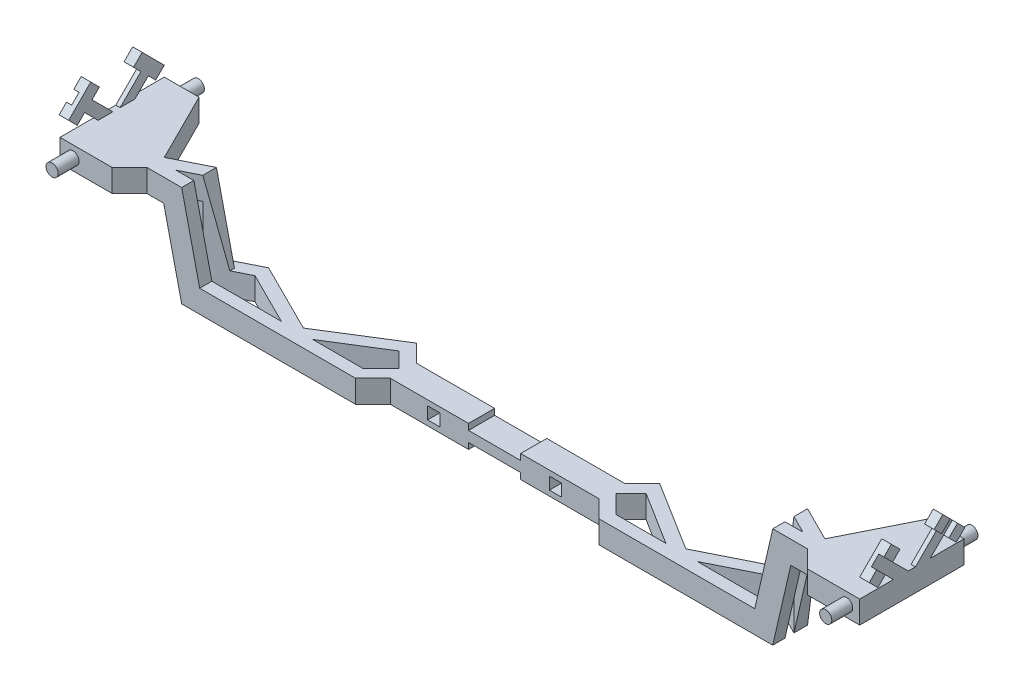
SolidWorks part; units mm, degrees
material "PBT General Purpose"
ref_plane "Front Plane" through (0, 0, 0) normal (0, 0, 1) x (1, 0, 0)
ref_plane "Top Plane" through (0, 0, 0) normal (0, 1, 0) x (1, 0, 0)
ref_plane "Right Plane" through (0, 0, 0) normal (1, 0, 0) x (0, 0, -1)
sketch "Sketch1" plane through (0, 0, 0) normal (0, -1, 0) x (0, 0, 1)
  line L1 (-15, -57.5) -> (15, -57.5)
  line L2 (-15, -57.5) -> (-15, 57.5)
  line L3 (-15, 57.5) -> (15, 57.5)
  line L4 (15, -57.5) -> (15, 57.5)
  line L5 (-15, -57.5) -> (15, 57.5) construction
  line L6 (-15, 57.5) -> (15, -57.5) construction
  point P0 (0, 0)
  dimension "D1" = 115
  dimension "D2" = 30
extrude "Boss-Extrude1" add sketch "Sketch1" against normal blind 6.5
sketch "Sketch2" plane through (0, 0, 0) normal (0, 0, 1) x (1, 0, 0)
  line L1 (-57.5, 3.25) -> (-53.75, 3.25) construction
  line L2 (-57.5, 6.5) -> (-57.5, 0) construction
  circle A0 centre (-53.75, 3.25) radius 1.75
  dimension "D1" = 3.5
  dimension "D2" = 3.75
extrude "Boss-Extrude2" add sketch "Sketch2" against normal blind 21.025 and the other way blind 21.025
sketch "Sketch3" [suppressed] plane through (-11.6078, -26.3195, 0) normal (0, 0, 1) x (-1, 0, 0)
  line L0 (38.3922, -32.8195) -> (38.3922, -26.3195) construction
  line L1 (38.1407, -29.5811) -> (31.4445, -29.9941) construction
  line L14 (37.9239, -29.0985) -> (34.3773, -25.5312)
  arc A1 (37.9753, -30.0988) -> (37.9239, -29.0985) centre (37.3921, -29.6273) ccw
  circle A2 centre (33.1422, -29.5695) radius 1.75 construction
  arc A5 (34.5556, -33.6079) -> (37.9753, -30.0988) centre (17.3684, -13.4374) ccw
  point P0 (38.3922, -29.5695)
  dimension "D1" = 1.5
sketch "Sketch4" plane through (-57.5, 0, 0) normal (-1, 0, 0) x (0, 0, 1)
  line L0 (0, -1000) -> (0, 49000) construction
  line L1 (15, 4.53) -> (15, 7.4362) construction
  line L2 (15, 7.4362) -> (17.009, 7.4362) construction
  line L3 (-9.1587, 10.3713) -> (-11.6392, 12.8374)
  line L4 (2.5, 22.03) -> (-2.5, 22.03) construction
  line L5 (-7.4017, 17.0996) -> (-13.7471, 10.7171)
  line L6 (-17.009, 7.4362) -> (-15, 7.4362) construction
  line L7 (-15, 7.4362) -> (-15, 4.53) construction
  line L8 (-11.28, 8.25) -> (-4.916, 14.614)
  line L9 (-2.5, 17.03) -> (2.5, 17.03) construction
  line L10 (-7.0374, 12.4926) -> (-9.5241, 14.9649)
  line L11 (0, 22.03) -> (0, 17.03) construction
  line L12 (15, 6.5) -> (-15, 6.5) construction
  line L13 (-7.4017, 17.0996) -> (-4.916, 14.614)
  line L14 (-13.7471, 10.7171) -> (-11.28, 8.25)
  line L15 (-9.1587, 10.3713) -> (0, 1.2126)
  line L16 (-7.0374, 12.4926) -> (0, 5.4553)
  line L17 (7.0374, 12.4926) -> (0, 5.4553)
  line L18 (9.1587, 10.3713) -> (0, 1.2126)
  line L19 (13.7471, 10.7171) -> (11.28, 8.25)
  line L20 (7.4017, 17.0996) -> (4.916, 14.614)
  line L21 (11.28, 8.25) -> (4.916, 14.614)
  line L22 (7.4017, 17.0996) -> (13.7471, 10.7171)
  line L23 (7.0374, 12.4926) -> (9.5241, 14.9649)
  line L24 (9.1587, 10.3713) -> (11.6392, 12.8374)
  line M3 (15, 6.5) -> (-15, 6.5)
  dimension "D1" = 10.53
  dimension "D2" = 3
  dimension "D3" = 9
  dimension "D4" = 3
  dimension "D5" = 1.75
extrude "Boss-Extrude3" add sketch "Sketch4" against normal blind 1.25 contours L18 L17 L16 L15 M3 | L18 L21 L17 M3 | L21 L24 L22 L23 | L21 L23 L22 L20 | L24 L21 L19 L22 | L16 L8 L15 M3 | L5 L14 L8 L3 | L8 L10 L5 L3 | L13 L5 L10 L8 region at (-57.5, 10.5437, -11.4551) region at (-57.5, 12.667, -9.3394) region at (-57.5, 9.004, -5.518) region at (-57.5, 14.7939, -7.2201) region at (-57.5, 4.6801, 0) region at (-57.5, 9.004, 5.518) region at (-57.5, 12.667, 9.3394) region at (-57.5, 14.7939, 7.2201) region at (-57.5, 10.5437, 11.4551)
extrude "Boss-Extrude4" add sketch "Sketch4<3>" along normal blind 1.5 contours L5 L14 L8 L3 | L13 L5 L10 L8 | L21 L23 L22 L20 | L24 L21 L19 L22 region at (-57.5, 10.5437, -11.4551) region at (-57.5, 14.7939, -7.2201) region at (-57.5, 10.5437, 11.4551) region at (-57.5, 14.7939, 7.2201)
sketch "Sketch4<3>" plane through (-57.5, 0, 0) normal (-1, 0, 0) x (0, 0, 1) same geometry as "Sketch4"
ref_plane "Plane1" through (57.5, 0, 0) normal (1, 0, 0) x (0, 0, -1)
mirror "Mirror1" about plane through (57.5, 0, 0) normal (1, 0, 0) of bodies 105
sketch "Sketch6" plane through (0, 6.5, 0) normal (0, 1, 0) x (1, 0, 0)
  line L0 (27.5, -5) -> (87.5, -5)
  line L1 (-57.5, 15) -> (172.5, 15) construction
  line L2 (-47.5, 15) -> (-37.5, -5)
  line L3 (87.5, -5) -> (92.5, -10)
  line L4 (92.5, -10) -> (152.5, -10)
  line L5 (152.5, -10) -> (157.5, -15)
  line L6 (172.5, -15) -> (-57.5, -15) construction
  line L7 (57.5, -55) -> (57.5, 55) construction
  line L8 (57.5, -997.6359) -> (57.5, 49002.3641) construction
  line L9 (-37.5, -10) -> (-42.5, -15)
  line L10 (22.5, -10) -> (-37.5, -10)
  line L11 (27.5, -5) -> (22.5, -10)
  line L12 (27.5, 2.5) -> (87.5, 2.5)
  line L13 (-37.5, -5) -> (-17.5, 5)
  line L14 (-17.5, 5) -> (2.5, -5)
  line L15 (2.5, -5) -> (22.5, 7.5)
  line L16 (22.5, 7.5) -> (27.5, 2.5)
  line L17 (162.5, 15) -> (152.5, -5)
  line L18 (152.5, -5) -> (132.5, 5)
  line L19 (132.5, 5) -> (112.5, -5)
  line L20 (112.5, -5) -> (92.5, 7.5)
  line L21 (92.5, 7.5) -> (87.5, 2.5)
  line L22 (-32.6738, -6.5) -> (-17.5, 1.0869)
  line L23 (-17.5, 1.0869) -> (-2.3262, -6.5)
  line L24 (6.7038, -6.5) -> (21.9939, 3.0563)
  line L25 (21.9939, 3.0563) -> (25.0251, 0.0251)
  line L26 (25.0251, -2.5251) -> (21.0503, -6.5)
  line L27 (21.0503, -6.5) -> (6.7038, -6.5)
  line L28 (21.0503, -6.5) -> (-37.5, -6.5) construction
  line L29 (-35.9348, -8.1305) -> (-17.5, 1.0869) construction
  line L30 (-17.5, 1.0869) -> (2.6904, -9.0083) construction
  line L31 (-2.3262, -6.5) -> (-32.6738, -6.5)
  line L32 (2.6904, -9.0083) -> (21.9939, 3.0563) construction
  line L33 (25.0251, 0.0251) -> (26.3003, -1.25)
  line L34 (25.0251, -2.5251) -> (26.3003, -1.25)
  line L35 (147.6738, -6.5) -> (132.5, 1.0869)
  line L36 (132.5, 1.0869) -> (117.3262, -6.5)
  line L37 (117.3262, -6.5) -> (147.6738, -6.5)
  line L38 (89.9749, -2.5251) -> (88.6997, -1.25)
  line L39 (89.9749, 0.0251) -> (88.6997, -1.25)
  line L40 (93.9497, -6.5) -> (108.2962, -6.5)
  line L41 (89.9749, -2.5251) -> (93.9497, -6.5)
  line L42 (93.0061, 3.0563) -> (89.9749, 0.0251)
  line L43 (108.2962, -6.5) -> (93.0061, 3.0563)
  point P18 (57.5, -5)
  line M18 (-57.5, -15) -> (172.5, -15)
  line M28 (172.5, 15) -> (-57.5, 15)
  dimension "D1" = 135
  dimension "D2" = 30
  dimension "D3" = 100
  dimension "D4" = 20
  dimension "D5" = 5
  dimension "D6" = 7.5
  dimension "D7" = 105
  dimension "D8" = 75
  dimension "D9" = 55
  dimension "D10" = 3.5
extrude "Cut-Extrude1" cut sketch "Sketch6" against normal through all and the other way through all contours L21 L20 L19 L18 L17 L2 L13 L14 L15 L16 L12 M28 | L0 L11 L10 L9 L5 L4 L3 M18 | L31 L23 L22 | L26 L34 L33 L25 L24 L27 | L40 L43 L42 L39 L38 L41 | L36 L37 L35 region at (57.5, 6.5, 11.2821) region at (57.5, 6.5, -7.8906) region at (-17.5, 6.5, 3.971) region at (18.2027, 6.5, 2.8805) region at (132.5, 6.5, 3.971) region at (96.7973, 6.5, 2.8805)
sketch "Sketch5" plane through (0, 0, -15) normal (0, 0, 1) x (1, 0, 0)
  line L1 (27.5, 6.5) -> (87.5, 6.5) construction
  line L2 (50, 8.25) -> (65, 8.25)
  line L3 (27.5, 3.25) -> (87.5, 3.25) construction
  line L4 (27.5, 0) -> (27.5, 6.5) construction
  line L5 (87.5, 0) -> (87.5, 6.5) construction
  line L6 (57.5, -982.6664) -> (57.5, 49017.3336) construction
  line L7 (57.5, -55) -> (57.5, 55) construction
  line L8 (50, 8.25) -> (50, 4.75)
  line L9 (38.25, 5) -> (41.75, 5)
  line L10 (38.25, 5) -> (38.25, 1.5)
  line L11 (38.25, 1.5) -> (41.75, 1.5)
  line L12 (41.75, 5) -> (41.75, 1.5)
  line L13 (38.25, 5) -> (41.75, 1.5) construction
  line L14 (38.25, 1.5) -> (41.75, 5) construction
  line L15 (50, 4.75) -> (65, 4.75)
  line L16 (65, 8.25) -> (65, 4.75)
  line L17 (50, 8.25) -> (65, 4.75) construction
  line L18 (50, 4.75) -> (65, 8.25) construction
  line L19 (76.75, 1.5) -> (73.25, 5) construction
  line L20 (76.75, 5) -> (73.25, 1.5) construction
  line L21 (73.25, 5) -> (73.25, 1.5)
  line L22 (76.75, 1.5) -> (73.25, 1.5)
  line L23 (76.75, 5) -> (76.75, 1.5)
  line L24 (76.75, 5) -> (73.25, 5)
  line L25 (50, 1.75) -> (65, -1.75) construction
  line L26 (50, -1.75) -> (65, 1.75) construction
  line L27 (65, -1.75) -> (65, 1.75)
  line L28 (50, 1.75) -> (65, 1.75)
  line L29 (50, -1.75) -> (50, 1.75)
  line L30 (50, -1.75) -> (65, -1.75)
  point P10 (40, 3.25)
  point P15 (57.5, 6.5)
  point P26 (75, 3.25)
  point P31 (57.5, 0)
  dimension "D1" = 3.5
  dimension "D2" = 3.5
  dimension "D3" = 15
  dimension "D4" = 17.5
extrude "Cut-Extrude3" cut sketch "Sketch5" along normal through all
ref_axis "Axis1" through (57.5, 4.75, 5) along (0, 0, -1)
sketch "Sketch8" plane through (0, 0, 0) normal (0, 1, 0) x (1, 0, 0)
  line L0 (-27.5, 9.6889) -> (-27.5, -15.3111)
  line L1 (57.5, -5) -> (57.5, 2.5) construction
  line L2 (142.5, 6.6895) -> (142.5, -18.3105)
  dimension "D1" = 85
  dimension "D2" = 25
  dimension "D3" = 85
split "Split1" trim tools "Sketch8" bodies to split 110 resulting bodies 111 112 113
move or copy body "Body-Move/Copy1" bodies to move or copy 111 copy no translate (0, -22.5, 0)
sketch "Sketch9" plane through (0, 0, 10) normal (0, 0, 1) x (1, 0, 0)
  line L0 (-27.5, -22.5) -> (-32.6748, 0)
  line L1 (-27.5, 0) -> (-37.5, 0) construction
  line L2 (-27.5, 6.5) -> (-22.3252, -16)
  line L3 (22.5, -16) -> (-27.5, -16) construction
  line L4 (-32.6748, 0) -> (-27.5, 6.5)
  line L5 (-27.5, -22.5) -> (-22.3252, -16)
  line L6 (57.5, -1001.6514) -> (57.5, 48998.3486) construction
  line L7 (57.5, -55) -> (57.5, 55) construction
  line L8 (142.5, -22.5) -> (137.3252, -16)
  line L9 (147.6748, 0) -> (142.5, 6.5)
  line L10 (142.5, 6.5) -> (137.3252, -16)
  line L11 (142.5, -22.5) -> (147.6748, 0)
  dimension "D1" = 6.5
extrude "Boss-Extrude10" add sketch "Sketch9" against normal up to surface (3.5 mm away) up to face at (-30.0869, 3.25, 6.5)
extrude "Boss-Extrude11" add sketch "Sketch9<3>" against normal up to vertex (10 mm away) from vertex up to point (-27.5, 6.5, 0) starting at point (-27.5, 6.5, 3.9131)
sketch "Sketch9<3>" plane through (0, 0, 10) normal (0, 0, 1) x (1, 0, 0) same geometry as "Sketch9"
sketch "Sketch11" plane through (0, 0, 0) normal (0, 1, 0) x (1, 0, 0)
  line L0 (57.5, -991.9144) -> (57.5, 49008.0856) construction
  line L1 (57.5, -5) -> (57.5, 2.5) construction
  line L2 (-37.5, -5) -> (-17.5, 5)
  line L3 (-17.5, 5) -> (-19.7361, 9.4721)
  line L4 (-19.7361, 9.4721) -> (-39.7361, -0.5279)
  line L5 (-47.5, 15) -> (-37.5, -5) construction
  line L6 (-39.7361, -0.5279) -> (-37.5, -5)
  line L7 (-17.5, 1.0869) -> (-32.6738, -6.5)
  line L8 (-32.6738, -6.5) -> (-2.3262, -6.5)
  line L9 (-2.3262, -6.5) -> (-17.5, 1.0869)
  line L10 (117.3262, -6.5) -> (132.5, 1.0869)
  line L11 (147.6738, -6.5) -> (117.3262, -6.5)
  line L12 (132.5, 1.0869) -> (147.6738, -6.5)
  line L13 (154.7361, -0.5279) -> (152.5, -5)
  line L14 (134.7361, 9.4721) -> (154.7361, -0.5279)
  line L15 (132.5, 5) -> (134.7361, 9.4721)
  line L16 (152.5, -5) -> (132.5, 5)
  dimension "D1" = 5
extrude "Cut-Extrude4" cut sketch "Sketch11" against normal through all both and the other way through all
equation "\"D1@Boss-Extrude2\"=\"D2@Boss-Extrude2\""
equation "\"D2@Sketch4\"=\"D3@Sketch4\"/3"
equation "\"D4@Sketch4\"=\"D2@Sketch4\""
equation "\"D3@Sketch8\"=\"D1@Sketch8\""
